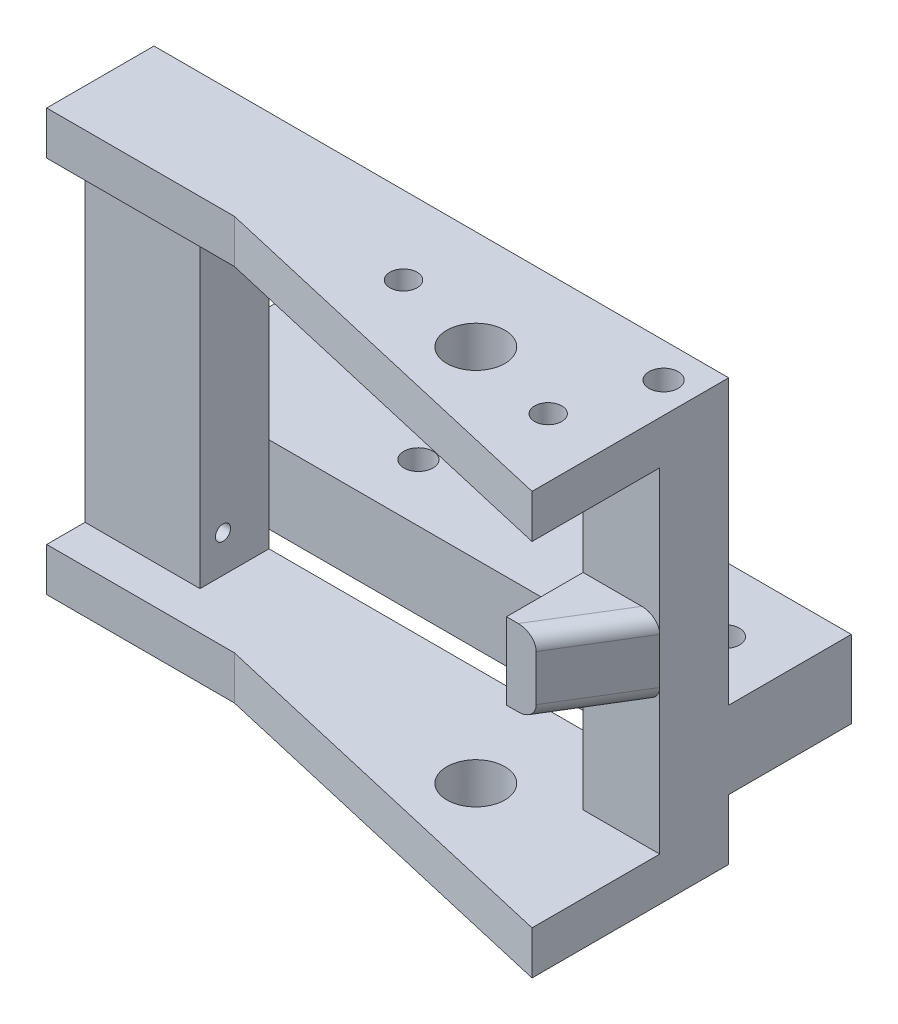
SolidWorks part; units mm, degrees
ref_plane "Front Plane" through (0, 0, 0) normal (0, 0, 1) x (1, 0, 0)
ref_plane "Top Plane" through (0, 0, 0) normal (0, 1, 0) x (1, 0, 0)
ref_plane "Right Plane" through (0, 0, 0) normal (1, 0, 0) x (0, 0, -1)
sketch "Sketch1" plane through (0, 0, 0) normal (0, 0, 1) x (1, 0, 0)
  line L1 (57.15, -34.925) -> (-57.15, -34.925)
  line L2 (57.15, -34.925) -> (57.15, 34.925)
  line L3 (57.15, 34.925) -> (-57.15, 34.925)
  line L4 (-57.15, -34.925) -> (-57.15, 34.925)
  line L5 (57.15, -34.925) -> (-57.15, 34.925) construction
  line L6 (57.15, 34.925) -> (-57.15, -34.925) construction
  point P0 (0, 0)
  dimension "D1" = 69.85
  dimension "D2" = 114.3
extrude "Boss-Extrude1" add sketch "Sketch1" along normal blind 57.15
sketch "Sketch2" plane through (0, 0, 57.15) normal (0, 0, 1) x (1, 0, 0)
  line L0 (-57.15, 34.925) -> (-57.15, -34.925) construction
  line L1 (57.15, -27.725) -> (-57.15, -27.725)
  line L2 (57.15, -27.725) -> (57.15, 27.725)
  line L3 (57.15, 27.725) -> (-57.15, 27.725)
  line L4 (-57.15, -27.725) -> (-57.15, 27.725)
  line L5 (57.15, -27.725) -> (-57.15, 27.725) construction
  line L6 (57.15, 27.725) -> (-57.15, -27.725) construction
  line L7 (57.15, 34.925) -> (-57.15, 34.925) construction
  point P0 (0, 0)
  dimension "D1" = 7.2
extrude "Cut-Extrude2" cut sketch "Sketch2" against normal blind 25.4
sketch "Sketch3" plane through (0, 0, 0) normal (0, 0, -1) x (-1, 0, 0)
  line L0 (-57.15, -34.925) -> (-57.15, 34.925) construction
  line L1 (57.15, 34.925) -> (-57.15, 34.925)
  line L2 (57.15, 34.925) -> (57.15, -12.065)
  line L3 (57.15, -12.065) -> (-57.15, -12.065)
  line L4 (-57.15, 34.925) -> (-57.15, -12.065)
  dimension "D1" = 46.99
extrude "Cut-Extrude3" cut sketch "Sketch3" against normal blind 20.32
sketch "Sketch5" plane through (0, -34.925, 0) normal (0, -1, 0) x (1, 0, 0)
  line L0 (-3.81, 10.79) -> (46.99, 10.79) construction
  line L1 (57.15, 20.32) -> (-57.15, 20.32) construction
  line L2 (57.15, 57.15) -> (57.15, 0) construction
  circle A0 centre (-3.81, 10.79) radius 2.415
  circle A1 centre (46.99, 10.79) radius 2.415
  dimension "D3" = 4.83
  dimension "D4" = 10.16
  dimension "D1" = 9.53
  dimension "D2" = 50.8
sketch "Sketch7" plane through (0, -34.925, 0) normal (0, -1, 0) x (1, 0, 0)
  line L0 (57.15, 57.15) -> (57.15, 0) construction
  line L2 (-57.15, 31.75) -> (57.15, 31.75) construction
  circle A0 centre (31.75, 36.83) radius 4.8
  dimension "D1" = 9.6
  dimension "D2" = 25.4
  dimension "D3" = 5.08
extrude "Cut-Extrude6" cut sketch "Sketch7" against normal up to surface (69.85 mm away) up to face at (0, 34.925, 38.735)
sketch "Sketch8" plane through (0, 34.925, 0) normal (0, 1, 0) x (1, 0, 0)
  line L0 (16.1601, -33.2308) -> (47.3399, -40.4292) construction
  line L1 (57.15, -31.75) -> (-57.15, -31.75) construction
  circle A0 centre (31.75, -36.83) radius 16 construction
  circle A1 centre (16.1601, -33.2308) radius 2.25
  circle A2 centre (47.3399, -40.4292) radius 2.25
  dimension "D1" = 32
  dimension "D2" = 4.5
  dimension "D3" = 13
sketch "Sketch9" plane through (0, 0, 31.75) normal (0, 0, 1) x (1, 0, 0)
  line L0 (57.15, 34.925) -> (-57.15, 34.925) construction
  line L5 (57.15, 27.725) -> (-57.15, 27.725) construction
  line L6 (-19.05, 27.725) -> (44.45, 27.725)
  line L7 (-19.05, 27.725) -> (-19.05, -27.725)
  line L8 (-19.05, -27.725) -> (44.45, -27.725)
  line L9 (44.45, 27.725) -> (44.45, -27.725)
  line L10 (-57.15, -27.725) -> (57.15, -27.725) construction
  line L11 (-57.15, 27.725) -> (-57.15, -27.725) construction
  line L12 (57.15, -27.725) -> (57.15, 27.725) construction
  line L13 (-57.15, -34.925) -> (-38.1, -34.925)
  line L14 (-57.15, -34.925) -> (-57.15, 34.925)
  line L15 (-57.15, 34.925) -> (-38.1, 34.925)
  line L16 (-38.1, -34.925) -> (-38.1, 34.925)
  line L17 (-57.15, -34.925) -> (-38.1, 34.925) construction
  line L18 (-57.15, 34.925) -> (-38.1, -34.925) construction
  line L19 (-57.15, -34.925) -> (57.15, -34.925) construction
  point P5 (-47.625, 0)
  dimension "D1" = 12.7
  dimension "25in" = 38.1
  dimension "D2" = 19.05
extrude "Cut-Extrude7" cut sketch "Sketch9" against normal through all both and the other way through all
extrude "Cut-Extrude8" cut sketch "Sketch8" against normal up to next
sketch "Sketch10" [suppressed] plane through (0, 0, 29.21) normal (0, 0, 1) x (1, 0, 0)
  line L1 (-30.607, -1.778) -> (-30.607, -6.604) construction
  circle A0 centre (-33.2489, -4.191) radius 2.286
  point P5 (-30.607, -4.191)
  dimension "D1" = 4.572
sketch "Sketch11" [suppressed] plane through (0, 0, 20.32) normal (0, 0, -1) x (-1, 0, 0)
  circle A0 centre (33.2489, -4.191) radius 2.286
  dimension "D1" = 4.572
extrude "Cut-Extrude9" [suppressed] cut sketch "Sketch11" against normal blind 3.81
sketch "Sketch12" plane through (-19.05, 0, 0) normal (1, 0, 0) x (0, 0, -1)
  line L0 (-31.75, -27.725) -> (-31.75, 27.725) construction
  line L1 (-27.94, -21.59) -> (-27.94, 21.59) construction
  line L2 (-20.32, 27.725) -> (-20.32, -12.065) construction
  circle A0 centre (-27.94, -21.59) radius 1.25
  circle A1 centre (-27.94, 21.59) radius 1.25
  point P0 (-31.75, 0)
  point P8 (-27.94, 0)
  dimension "D1" = 2.5
  dimension "D2" = 7.62
  dimension "D3" = 43.18
extrude "Cut-Extrude10" cut sketch "Sketch12" against normal up to surface (19.05 mm away) up to face at (-38.1, -2.413, 33.274)
sketch "Sketch13" plane through (0, 34.925, 0) normal (0, 1, 0) x (1, 0, 0)
  line L0 (-38.1, -38.1077) -> (-6.9983, -38.1077)
  line L1 (-6.9983, -38.1077) -> (75.4829, -57.15)
  line L2 (57.15, -57.15) -> (-38.1, -57.15) construction
  line L3 (47.3399, -40.4292) -> (16.1601, -33.2308) construction
  line L4 (-38.1, -38.1077) -> (-38.1, -57.15)
  line L5 (-38.1, -57.15) -> (75.4829, -57.15)
  line L6 (-38.1, -20.32) -> (-38.1, -57.15) construction
extrude "Cut-Extrude12" cut sketch "Sketch13" against normal through all
sketch "Sketch14" plane through (44.45, 0, 0) normal (-1, 0, 0) x (0, 0, 1)
  line L0 (0, -27.725) -> (31.75, -27.725) construction
  line L1 (20.32, -12.065) -> (0, -12.065)
  line L2 (20.32, -12.065) -> (20.32, -27.725)
  line L3 (20.32, -27.725) -> (0, -27.725)
  line L4 (0, -12.065) -> (0, -27.725)
extrude "Boss-Extrude2" add sketch "Sketch14" along normal up to next
sketch "Sketch16" plane through (0, 0, 31.75) normal (0, 0, 1) x (1, 0, 0)
  line L0 (44.45, -27.725) -> (44.45, 27.725) construction
  line L1 (57.15, -6.35) -> (44.45, -6.35)
  line L2 (57.15, -6.35) -> (57.15, 6.35)
  line L3 (57.15, 6.35) -> (44.45, 6.35)
  line L4 (44.45, -6.35) -> (44.45, 6.35)
  line L5 (57.15, -6.35) -> (44.45, 6.35) construction
  line L6 (57.15, 6.35) -> (44.45, -6.35) construction
  line L7 (57.15, 6.35) -> (57.15, -6.35) construction
  line L9 (57.15, -27.725) -> (57.15, 27.725) construction
  point P0 (50.8, 0)
  point P7 (57.15, 0)
  dimension "D1" = 12.7
extrude "Boss-Extrude3" add sketch "Sketch16" along normal blind 12.7
sketch "Sketch17" plane through (0, 6.35, 0) normal (0, 1, 0) x (1, 0, 0)
  line L0 (49.375, -44.45) -> (57.15, -31.75)
  line L1 (57.15, -44.45) -> (57.15, -31.75) construction
  line L2 (57.15, -31.75) -> (44.45, -31.75) construction
  line L3 (57.15, -31.75) -> (57.15, -44.45)
  line L4 (57.15, -44.45) -> (49.375, -44.45)
  line L5 (57.15, -44.45) -> (44.45, -44.45) construction
extrude "Cut-Extrude14" cut sketch "Sketch17" against normal blind 12.7
fillet "Fillet4" radius 2.54 2 edges at (53.2625, -6.35, 38.1) (53.2625, 6.35, 38.1)
sketch "Sketch18" plane through (-38.1, 0, 0) normal (-1, 0, 0) x (0, 0, 1)
  line L0 (0, -34.925) -> (38.1077, -34.925) construction
  line L1 (20.32, -35.0627) -> (20.32, -24.9001)
  line L2 (20.32, -24.9001) -> (0, -24.9001)
  line L3 (0, -34.925) -> (0, -12.065) construction
  line L4 (0, -24.9001) -> (0, -34.925)
  line L5 (20.32, -34.925) -> (0, -34.925)
  point P0 (20.32, -34.925)
  point P1 (7.9478, 3.6724)
  line M3 (0, -34.925) -> (38.1077, -34.925)
  line M12 (0, -12.065) -> (0, -34.925)
sketch "Sketch19" plane through (-38.1, 0, 0) normal (-1, 0, 0) x (0, 0, 1)
  line L0 (20.32, -34.925) -> (0, -34.925)
sketch "Sketch20" plane through (-38.1, 0, 0) normal (-1, 0, 0) x (0, 0, 1)
  line L0 (0, -34.925) -> (38.1077, -34.925) construction
  line L1 (20.066, -34.925) -> (20.066, -24.765)
  line L2 (20.066, -24.765) -> (0, -24.765)
  line L3 (0, -34.925) -> (0, -12.065) construction
  line L4 (0, -24.765) -> (0, -34.925)
  line L5 (20.066, -34.925) -> (-0.1509, -34.925)
  point P0 (20.32, -34.925)
  dimension "D1" = 10.16
  dimension "D2" = 20.066
extrude "Cut-Extrude20" cut sketch "Sketch5" against normal through all contours A0 | A1
sketch "Sketch21" plane through (-38.1, 0, 0) normal (-1, 0, 0) x (0, 0, 1)
sketch "Sketch22" plane through (-38.1, 0, 0) normal (-1, 0, 0) x (0, 0, 1)
extrude "Cut-Extrude21" cut sketch "Sketch18" against normal through all contours L1 L2 M12 M3 region at (-38.1, -29.9125, 10.16)
sketch "Sketch23" plane through (0, -34.925, 0) normal (0, -1, 0) x (1, 0, 0)
  line L0 (57.15, 20.32) -> (57.15, 31.75)
  line L1 (57.15, 52.9175) -> (57.15, 20.32) construction
  circle A0 centre (52.07, 26.035) radius 2.413
  point P7 (57.15, 26.035)
  point P8 (0, 0)
  dimension "D2" = 4.826
  dimension "D1" = 11.43
  dimension "D3" = 5.08
extrude "Cut-Extrude22" cut sketch "Sketch23" against normal through all contours A0
